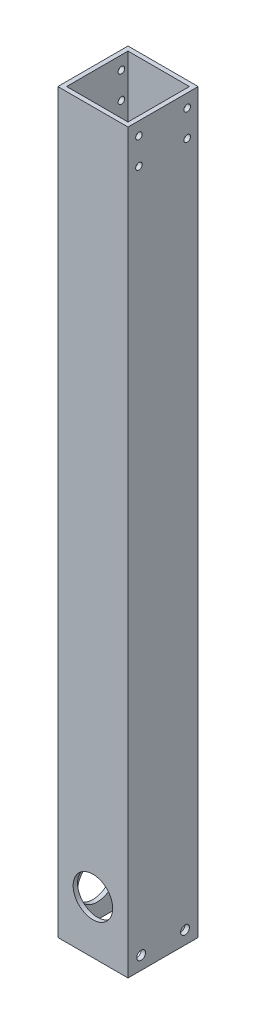
SolidWorks part; units mm, degrees
material "6063-T1"
ref_plane "Front Plane" through (0, 0, 0) normal (0, 0, 1) x (1, 0, 0)
ref_plane "Top Plane" through (0, 0, 0) normal (0, 1, 0) x (1, 0, 0)
ref_plane "Right Plane" through (0, 0, 0) normal (1, 0, 0) x (0, 0, -1)
sketch "Sketch1" plane through (0, 0, 0) normal (0, 1, 0) x (1, 0, 0)
  line L1 (-25.4, 25.4) -> (25.4, 25.4)
  line L2 (-25.4, 25.4) -> (-25.4, -25.4)
  line L3 (-25.4, -25.4) -> (25.4, -25.4)
  line L4 (25.4, 25.4) -> (25.4, -25.4)
  line L5 (-25.4, 25.4) -> (25.4, -25.4) construction
  line L6 (-25.4, -25.4) -> (25.4, 25.4) construction
  line L7 (-22.225, -22.225) -> (22.225, -22.225)
  line L8 (-22.225, -22.225) -> (-22.225, 22.225)
  line L9 (-22.225, 22.225) -> (22.225, 22.225)
  line L10 (22.225, -22.225) -> (22.225, 22.225)
  line L11 (-22.225, -22.225) -> (22.225, 22.225) construction
  line L12 (-22.225, 22.225) -> (22.225, -22.225) construction
  point P0 (0, 0)
  point P6 (0, 0)
  dimension "D1" = 50.8
  dimension "D2" = 50.8
  dimension "D3" = 3.175
  dimension "D4" = 3.175
extrude "Boss-Extrude1" add sketch "Sketch1" along normal blind 533.4
sketch "Sketch2" plane through (-25.4, 0, 0) normal (-1, 0, 0) x (0, 0, 1)
  line L0 (-25.4, 0) -> (25.4, 0) construction
  circle A0 centre (0, 25.4) radius 14.2875
  dimension "D1" = 28.575
  dimension "D2" = 25.4
extrude "Cut-Extrude1" cut sketch "Sketch2" against normal blind 3.175
sketch "Sketch3" plane through (0, 0, -25.4) normal (0, 0, -1) x (-1, 0, 0)
  line L0 (-25.4, 0) -> (25.4, 0) construction
  circle A0 centre (0, 38.1) radius 14.3002
  dimension "D1" = 28.6004
  dimension "D2" = 38.1
extrude "Cut-Extrude2" cut sketch "Sketch3" against normal through all
sketch "Sketch4" plane through (-25.4, 0, 0) normal (-1, 0, 0) x (0, 0, 1)
  line L0 (25.4, 533.4) -> (25.4, 0) construction
  line L1 (-25.4, 533.4) -> (25.4, 533.4) construction
  line L2 (0, 533.4) -> (0, 0) construction
  line L3 (-25.4, 0) -> (25.4, 0) construction
  circle A0 centre (17.4625, 523.875) radius 2.3813
  circle A1 centre (17.4625, 504.825) radius 2.3813
  circle A2 centre (-17.4625, 504.825) radius 2.3813
  circle A3 centre (-17.4625, 523.875) radius 2.3813
  dimension "D1" = 4.7625
  dimension "D2" = 7.9375
  dimension "D4" = 4.7625
  dimension "D3" = 9.525
  dimension "D5" = 19.05
extrude "Cut-Extrude3" cut sketch "Sketch4" against normal through all
sketch "Sketch5" plane through (-25.4, 0, 0) normal (-1, 0, 0) x (0, 0, 1)
  line L0 (-25.4, 0) -> (25.4, 0) construction
  line L1 (-25.4, 533.4) -> (-25.4, 0) construction
  line L2 (0, 0) -> (0, 28.4143) construction
  circle A0 centre (-15.875, 9.525) radius 3.175
  circle A1 centre (15.875, 9.525) radius 3.175
  dimension "D1" = 6.35
  dimension "D2" = 9.525
  dimension "D3" = 9.525
extrude "Cut-Extrude4" cut sketch "Sketch5" against normal through all
